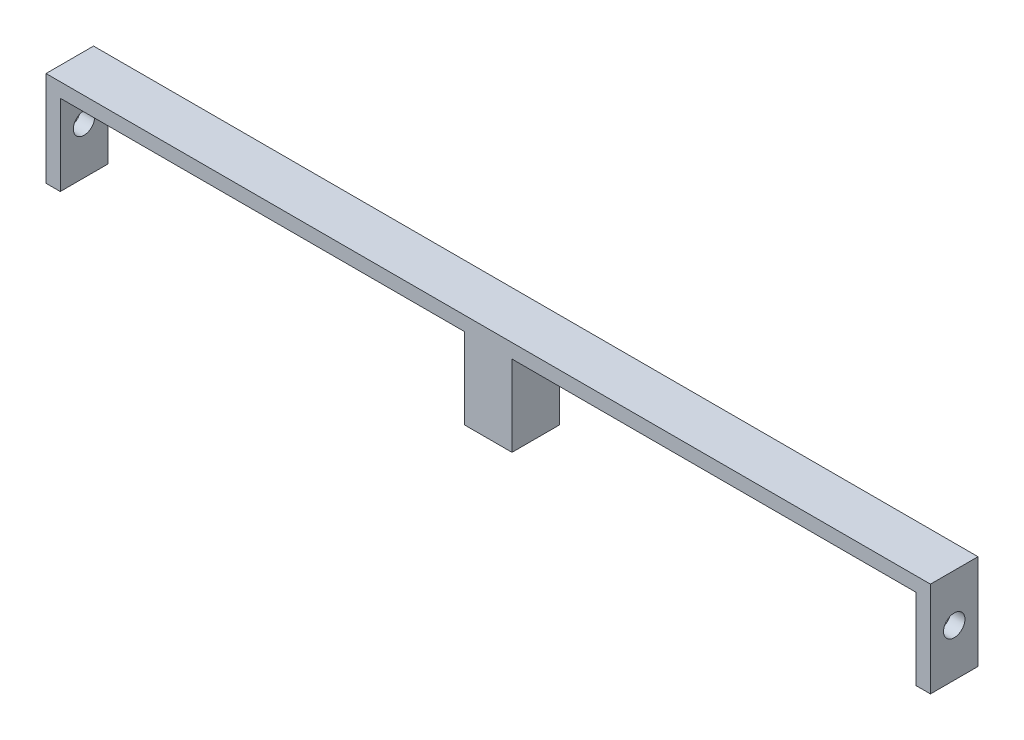
SolidWorks part; units mm, degrees
ref_plane "Płaszczyzna przednia" through (0, 0, 0) normal (0, 0, 1) x (1, 0, 0)
ref_plane "Płaszczyzna górna" through (0, 0, 0) normal (0, 1, 0) x (1, 0, 0)
ref_plane "Płaszczyzna prawa" through (0, 0, 0) normal (1, 0, 0) x (0, 0, -1)
sketch "Szkic2" plane through (0, 0, 0) normal (0, 0, 1) x (1, 0, 0)
  line L0 (-60.4346, 22.6891) -> (125.5654, 22.6891)
  line L1 (125.5654, 22.6891) -> (125.5654, 2.6891)
  line L2 (125.5654, 2.6891) -> (122.5654, 2.6891)
  line L3 (122.5654, 2.6891) -> (122.5654, 19.6891)
  line L4 (122.5654, 19.6891) -> (37.5654, 19.6891)
  line L5 (-57.4346, 19.6891) -> (-57.4346, 2.6891)
  line L6 (-57.4346, 2.6891) -> (-60.4346, 2.6891)
  line L7 (-60.4346, 2.6891) -> (-60.4346, 22.6891)
  line L8 (27.5654, 19.6891) -> (-57.4346, 19.6891)
  line L10 (27.5654, 19.6891) -> (27.5654, 2.6891)
  line L11 (27.5654, 2.6891) -> (37.5654, 2.6891)
  line L12 (37.5654, 19.6891) -> (37.5654, 2.6891)
  point P9 (32.5654, 22.6891)
  dimension "D1" = 20
  dimension "D2" = 20
  dimension "D3" = 3
  dimension "D4" = 3
  dimension "D5" = 3
  dimension "D6" = 10
  dimension "D7" = 5
  dimension "D8" = 186
extrude "Dodanie-wyciągnięcie1" add sketch "Szkic2" along normal blind 10
sketch "Szkic4" plane through (-60.4346, 0, 0) normal (-1, 0, 0) x (0, 0, 1)
  line L0 (10, 2.6891) -> (0, 2.6891) construction
  line L1 (0, 22.6891) -> (0, 2.6891) construction
  circle A0 centre (5, 12.6891) radius 2.25
  dimension "D1" = 4.5
  dimension "D2" = 10
  dimension "D3" = 5
extrude "Wytnij-wyciągnięcie1" cut sketch "Szkic4" against normal blind 10
extrude "Wytnij-wyciągnięcie2" cut sketch "Szkic4<2>" against normal blind 10 from surface starting at face at (122.5654, 11.1891, 5)
sketch "Szkic4<2>" plane through (-60.4346, 0, 0) normal (-1, 0, 0) x (0, 0, 1) same geometry as "Szkic4"
